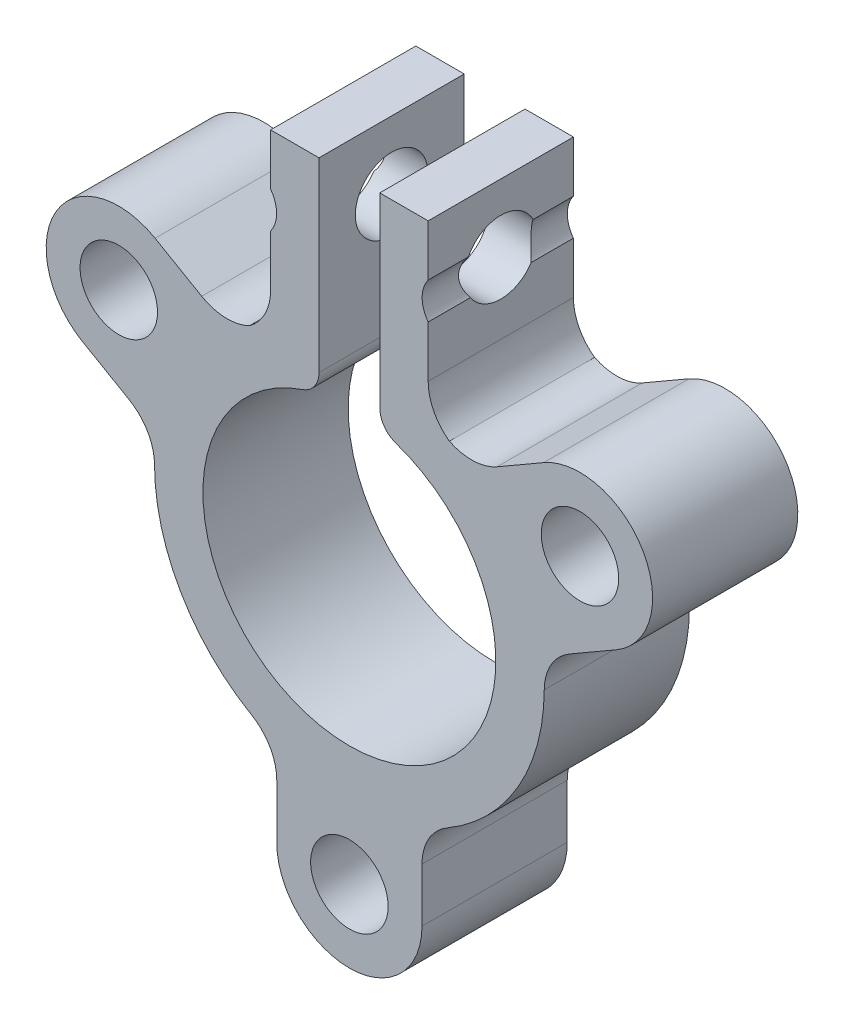
SolidWorks part; units mm, degrees
ref_plane "正面" through (0, 0, 0) normal (0, 0, 1) x (1, 0, 0)
ref_plane "平面" through (0, 0, 0) normal (0, 1, 0) x (1, 0, 0)
ref_plane "右側面" through (0, 0, 0) normal (1, 0, 0) x (0, 0, -1)
sketch "ｽｹｯﾁ1" plane through (0, 0, 0) normal (0, 0, 1) x (1, 0, 0)
  line L0 (-1.255, 5.9184) -> (-1.255, 14.3626)
  line L1 (-1.255, 14.3626) -> (-3.255, 14.3626)
  line L2 (-3.255, 14.3626) -> (-3.255, 7.3626)
  line L3 (1.255, 5.9184) -> (1.255, 14.3626)
  line L4 (1.255, 14.3626) -> (3.255, 14.3626)
  line L5 (3.255, 14.3626) -> (3.255, 7.3626)
  line L6 (0, 0) -> (0, 14.3626) construction
  line L7 (-1.255, 14.3626) -> (1.255, 14.3626) construction
  arc A0 (1.255, 5.9184) -> (-1.255, 5.9184) centre (0, 0) cw
  arc A1 (3.255, 7.3626) -> (-3.255, 7.3626) centre (0, 0) cw
  point P12 (0, 14.3626)
  dimension "D1" = 6.05
  dimension "D2" = 2
  dimension "D3" = 2.51
  dimension "D4" = 2
  dimension "D5" = 7
extrude "ﾎﾞｽ - 押し出し1" add sketch "ｽｹｯﾁ1" along normal blind 6
sketch "ｽｹｯﾁ2" plane through (3.255, 0, 0) normal (1, 0, 0) x (0, 0, -1)
  line L0 (-3, 7.3626) -> (-3, 14.3626) construction
  line L1 (-6, 7.3626) -> (0, 7.3626) construction
  line L2 (-6, 14.3626) -> (0, 14.3626) construction
  circle A0 centre (-3, 11.5626) radius 1.5
  dimension "D1" = 3
  dimension "D2" = 2.8
extrude "ｶｯﾄ - 押し出し1" cut sketch "ｽｹｯﾁ2" against normal through all
sketch "ｽｹｯﾁ3" plane through (0, 0, 6) normal (0, 0, 1) x (1, 0, 0)
  line L0 (0, 0) -> (-9.5263, 5.5) construction
  line L2 (-4.9693, 6.3331) -> (-8.0263, 8.0981)
  line L3 (-6.4978, 7.2156) -> (-9.4978, 2.0195) construction
  line L4 (0, 0) -> (0, -6.05) construction
  line L5 (-11.0263, 2.9019) -> (-7.9693, 1.137)
  line L7 (8.0263, 8.0981) -> (4.9693, 6.3331)
  line L8 (7.9693, 1.137) -> (11.0263, 2.9019)
  line L9 (3, -11) -> (3, -7.4701)
  line L10 (-3, -7.4701) -> (-3, -11)
  arc A0 (-3.255, 7.3626) -> (3.255, 7.3626) centre (0, 0) ccw construction
  arc A1 (-4.9693, 6.3331) -> (-7.9693, 1.137) centre (0, 0) ccw
  arc A3 (-8.0263, 8.0981) -> (-11.0263, 2.9019) centre (-9.5263, 5.5) ccw
  circle A4 centre (-9.5263, 5.5) radius 1.6
  arc A5 (-1.255, 5.9184) -> (1.255, 5.9184) centre (0, 0) ccw construction
  arc A8 (7.9693, 1.137) -> (4.9693, 6.3331) centre (0, 0) ccw
  arc A9 (11.0263, 2.9019) -> (8.0263, 8.0981) centre (9.5263, 5.5) ccw
  circle A10 centre (9.5263, 5.5) radius 1.6
  arc A11 (-3, -7.4701) -> (3, -7.4701) centre (0, 0) ccw
  arc A12 (-3, -11) -> (3, -11) centre (0, -11) ccw
  circle A13 centre (0, -11) radius 1.6
  point P14 (-7.9978, 4.6175)
  dimension "D1" = 3.2
  dimension "D2" = 3
  dimension "D3" = 120
  dimension "D4" = 11
  dimension "D5" = 3
extrude "ﾎﾞｽ - 押し出し2" add sketch "ｽｹｯﾁ3" against normal through all
fillet "ﾌｨﾚｯﾄ1" radius 2.1 8 edges at (3.255, 7.3626, 3) (-7.9693, 1.137, 3) (-4.9693, 6.3331, 3) (-3.255, 7.3626, 3) (-3, -7.4701, 3) (3, -7.4701, 3) (7.9693, 1.137, 3) (4.9693, 6.3331, 3)
fillet "ﾌｨﾚｯﾄ2" radius 1 2 edges at (1.255, 5.9184, 3) (-1.255, 5.9184, 3)
sketch "ｽｹｯﾁ4" plane through (0, 0, 6) normal (0, 0, 1) x (1, 0, 0)
  line L0 (-3.255, 11.4925) -> (3.255, 11.4925) construction
  line L1 (-3.255, 14.3626) -> (-3.255, 8.6224) construction
  line L2 (3.255, 8.6224) -> (3.255, 14.3626) construction
  line L3 (4.255, 11.4925) -> (3.255, 11.4925) construction
  line L4 (0, 14.5061) -> (0, 0) construction
  circle A0 centre (4.255, 11.4925) radius 1.25
  circle A1 centre (-4.255, 11.4925) radius 1.25
  dimension "D1" = 1
  dimension "D2" = 2.5
extrude "ｶｯﾄ - 押し出し2" cut sketch "ｽｹｯﾁ4" against normal through all
